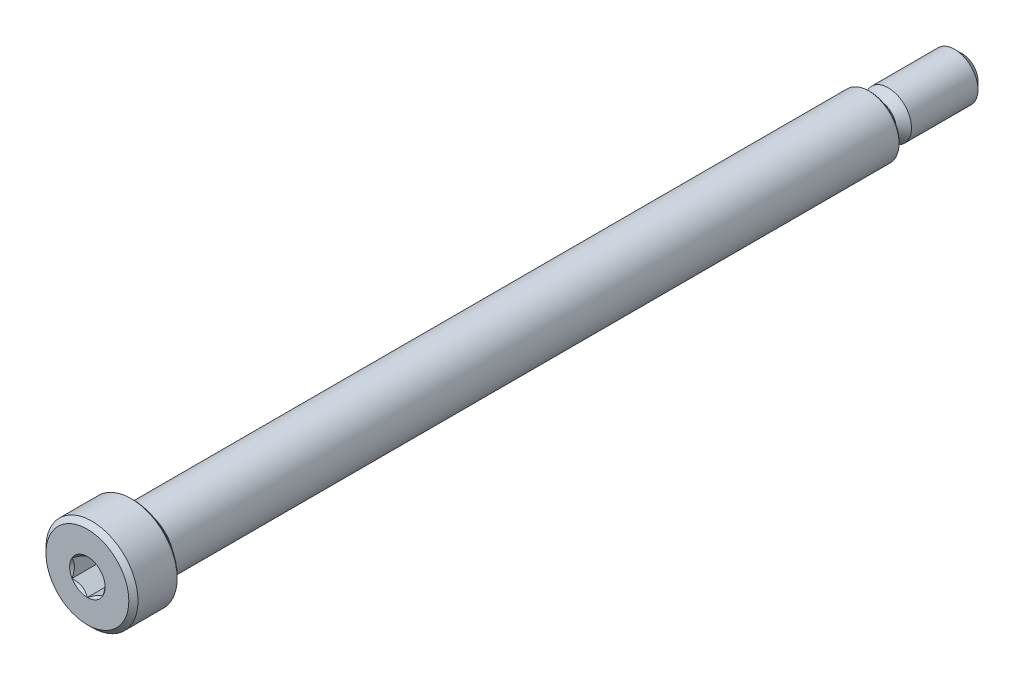
SolidWorks part; units mm, degrees
material "Cast Alloy Steel"
ref_plane "Front Plane" through (0, 0, 0) normal (0, 0, 1) x (1, 0, 0)
ref_plane "Top Plane" through (0, 0, 0) normal (0, 1, 0) x (1, 0, 0)
ref_plane "Right Plane" through (0, 0, 0) normal (1, 0, 0) x (0, 0, -1)
sketch "Sketch1" plane through (0, 0, 0) normal (0, 0, 1) x (1, 0, 0)
  line L1 (0, 1.8331) -> (-1.5875, 0.9165)
  line L2 (-1.5875, 0.9165) -> (-1.5875, -0.9165)
  line L3 (-1.5875, -0.9165) -> (0, -1.8331)
  line L4 (0, -1.8331) -> (1.5875, -0.9165)
  line L5 (1.5875, -0.9165) -> (1.5875, 0.9165)
  line L6 (1.5875, 0.9165) -> (0, 1.8331)
  circle A0 centre (0, 0) radius 4.7625
  circle A1 centre (0, 0) radius 1.5875 construction
  point P3 (0, 4.7625)
  point P11 (0, -4.7625)
  dimension "Head Diameter" = 9.525
  dimension "Drive Size" = 3.175
sketch "Sketch2" plane through (0, 0, 0) normal (1, 0, 0) x (0, 0, -1)
  line L0 (-45.2437, 0) -> (45.2438, 0) construction
  point P2 (0, 0)
  point P4 (-40.4812, 0)
  point P5 (35.7187, 0)
  point P6 (-40.4813, -3.1369)
  point P7 (-42.1481, 0)
  point P8 (44.1854, 0)
  point P9 (43.6562, -2.413)
  point P10 (45.2438, 2.413)
  point P12 (45.2438, -2.413)
  point P15 (-39.4229, -3.1369)
  dimension "Head Height" = 4.7625
  dimension "Shoulder Length" = 76.2
  dimension "Thread Length" = 9.525
  dimension "Screw Size Decimal Equivalent" = 4.826
  dimension "Thread Pitch" = 1.0583
  dimension "D1" = 3.0956
  dimension "D2" = 1.5875
  dimension "D3" = 1.0583
  dimension "Shoulder Diameter" = 6.2738
sketch "Sketch3" plane through (0, 0, 0) normal (1, 0, 0) x (0, 0, -1)
  line L0 (-45.2437, 0) -> (-45.2437, 4.2862)
  line L1 (-44.7675, 4.7625) -> (-40.7194, 4.7625)
  line L2 (-40.4812, 4.5244) -> (-40.4812, 3.0977)
  line L3 (-40.3636, 2.9801) -> (-39.5798, 2.9801)
  line L4 (-39.4229, 2.9801) -> (-39.4229, 3.1369) construction
  line L5 (-39.4229, 3.1369) -> (35.5619, 3.1369)
  line L6 (36.1156, 1.6192) -> (36.1156, 2.413) construction
  line L7 (-45.2437, 0) -> (45.2438, 0)
  line L8 (35.7187, 2.9801) -> (35.7187, 2.0161)
  line L9 (36.1156, 1.6192) -> (36.7771, 1.6192)
  line L10 (36.7771, 1.6192) -> (37.5708, 2.413)
  line L11 (37.5708, 2.413) -> (44.45, 2.413)
  line L12 (44.45, 2.413) -> (45.2438, 1.6192)
  line L13 (45.2438, 1.6192) -> (45.2438, 0)
  line L14 (-45.2437, 4.2862) -> (-44.7675, 4.7625)
  line L15 (-40.7194, 4.7625) -> (-40.4812, 4.5244)
  line L16 (-44.7675, 4.7625) -> (-44.7675, 4.5244) construction
  line L17 (-44.7675, 4.5244) -> (-44.7675, 4.2862) construction
  line L18 (-40.3636, 2.9801) -> (-40.3636, 3.0193) construction
  line L19 (-40.3636, 3.0193) -> (-40.3636, 3.0585) construction
  line L20 (-40.3636, 3.0585) -> (-40.3636, 3.0977) construction
  line L21 (-40.3636, 3.0977) -> (-40.3636, 3.1369) construction
  line L22 (-39.4229, 3.1369) -> (-39.5798, 2.9801)
  line L23 (35.5619, 3.1369) -> (35.7187, 2.9801)
  arc A0 (-40.4812, 3.0977) -> (-40.3636, 2.9801) centre (-40.3636, 3.0977) ccw
  arc A1 (35.7187, 2.0161) -> (36.1156, 1.6192) centre (36.1156, 2.0161) ccw
  point P3 (-44.5294, 4.7625)
  point P11 (-42.6244, 4.7625)
  point P35 (36.1156, 2.0161)
  dimension "D1" = 3.1369
  dimension "D2" = 2.9801
  dimension "D5" = 2.413
  dimension "D6" = 45
  dimension "D7" = 0.7938
  dimension "D8" = 0.4763
  dimension "D4" = 1.0583
  dimension "D9" = 0.2381
  dimension "D10" = 1.905
revolve "Revolve1" add sketch "Sketch3" angle 360 about L7
sketch "Sketch4" plane through (0, 0, 45.2437) normal (0, 0, 1) x (1, 0, 0)
  line L0 (-1.5875, -0.9165) -> (0, -1.8331) construction
  line L1 (-1.5875, 0.9165) -> (-1.5875, -0.9165) construction
  line L2 (0, 1.8331) -> (-1.5875, 0.9165) construction
  line L3 (1.5875, 0.9165) -> (0, 1.8331) construction
  line L4 (1.5875, -0.9165) -> (1.5875, 0.9165) construction
  line L5 (0, -1.8331) -> (1.5875, -0.9165) construction
  line L6 (-1.5875, -0.9165) -> (0, -1.8331)
  line L7 (-1.5875, 0.9165) -> (-1.5875, -0.9165)
  line L8 (0, 1.8331) -> (-1.5875, 0.9165)
  line L9 (1.5875, 0.9165) -> (0, 1.8331)
  line L10 (1.5875, -0.9165) -> (1.5875, 0.9165)
  line L11 (0, -1.8331) -> (1.5875, -0.9165)
extrude "Cut-Extrude1" cut sketch "Sketch4" against normal up to vertex (3.0956 mm away) up to point (0, 0, 42.1481)
sketch "Sketch5" plane through (0, 0, 45.2437) normal (0, 0, 1) x (1, 0, 0)
  circle A0 centre (0, 0) radius 1.8331
extrude "Cut-Extrude2" cut sketch "Sketch5" against normal up to vertex (3.0956 mm away) draft 45 up to point (0, 0, 42.1481)
ref_plane "Plane1" [suppressed] through (0, 0, -36.7771) normal (0, 0, 1) x (1, 0, 0)
split "Split1" [suppressed] bodies to split 106
sketch "Sketch6" [suppressed] plane through (0, 0, -45.2438) normal (0, 0, -1) x (-1, 0, 0)
  circle A0 centre (0, 0) radius 2.413 construction
  circle A1 centre (0, 0) radius 2.413
curve "Helix/Spiral1" [suppressed] pitch 1.0583 height 9.525 turns 9
sketch "Sketch7" [suppressed] plane through (0, 0, 0) normal (1, 0, 0) x (0, 0, -1)
  line L0 (45.1776, 2.5276) -> (45.7068, 1.611) construction
  line L1 (45.7068, 1.611) -> (46.2359, 2.5276) construction
  line L2 (46.2359, 2.5276) -> (45.1776, 2.5276) construction
  line L3 (45.2107, 2.4703) -> (46.2029, 2.4703)
  line L4 (46.2029, 2.4703) -> (45.7729, 1.7256)
  line L5 (45.7729, 1.7256) -> (45.6406, 1.7256)
  line L6 (45.6406, 1.7256) -> (45.2107, 2.4703)
  line L7 (45.7068, 1.7256) -> (45.7068, 1.611) construction
  line L8 (45.2438, 2.413) -> (46.1698, 2.413) construction
  line L9 (45.7068, 2.5276) -> (45.7068, 2.413) construction
  point P12 (45.7068, 2.4703)
  dimension "D1" = 1.0583
  dimension "D2" = 0.1323
sweep "Cut-Sweep1" [suppressed] cut profiles "Sketch7" path "Helix/Spiral1"
combine bodies "Combine1" [suppressed] operation type add bodies to combine 109 108
sketch "Sketch8" [suppressed] plane through (0, 0, 45.2437) normal (0, 0, 1) x (1, 0, 0)
  line L0 (0, 0) -> (0, 4.7625) construction
  line L1 (-0.1247, 4.7625) -> (0.1247, 4.7625)
  line L2 (0, 0) -> (-0.1247, 4.7625) construction
  line L3 (0.1247, 4.7625) -> (0, 0) construction
  line L4 (-0.1247, 4.7625) -> (0, 4.5465)
  line L5 (0, 4.5465) -> (0.1247, 4.7625)
  circle A0 centre (0, 0) radius 4.7625 construction
  point P7 (0, 4.7625)
  dimension "D1" = 1.5
extrude "Cut-Extrude3" [suppressed] cut sketch "Sketch8" against normal up to vertex from vertex
pattern_circular "CirPattern1" [suppressed] count 96 over 360 about axis through (0, 0, 45.2437) along (0, 0, -1) of bodies 111
equation "\"D1@Sketch2\"=0.65*\"Head Height@Sketch2\""
equation "\"D2@Sketch2\"=\"Thread Pitch@Sketch2\"*1.5"
equation "\"D1@Sketch3\"=0.5*\"Shoulder Diameter@Sketch2\""
equation "\"D2@Sketch3\"=0.95*\"D1@Sketch3\""
equation "\"D5@Sketch3\"=0.5*\"Screw Size Decimal Equivalent@Sketch2\""
equation "\"D7@Sketch3\"=0.75*\"Thread Pitch@Sketch2\""
equation "\"D8@Sketch3\"=0.05*\"Head Diameter@Sketch1\""
equation "\"D4@Sketch3\"=\"Thread Pitch@Sketch2\""
equation "\"D4@Helix/Spiral1\"=\"Thread Pitch@Sketch2\""
equation "\"D3@Helix/Spiral1\"=\"Thread Length@Sketch2\""
equation "\"D2@Sketch7\"=\"D1@Sketch7\"/8"
equation "\"D1@Sketch7\"=\"Thread Pitch@Sketch2\""
equation "\"D9@Sketch3\"=.05*\"Head Height@Sketch2\""
equation "\"D10@Sketch3\"=.4*\"Head Height@Sketch2\""
equation "\"D1@CirPattern1\"=360/(2*\"D1@Sketch8\"*1.25)"
equation "\"D3@Sketch2\"=\"Thread Pitch@Sketch2\""
